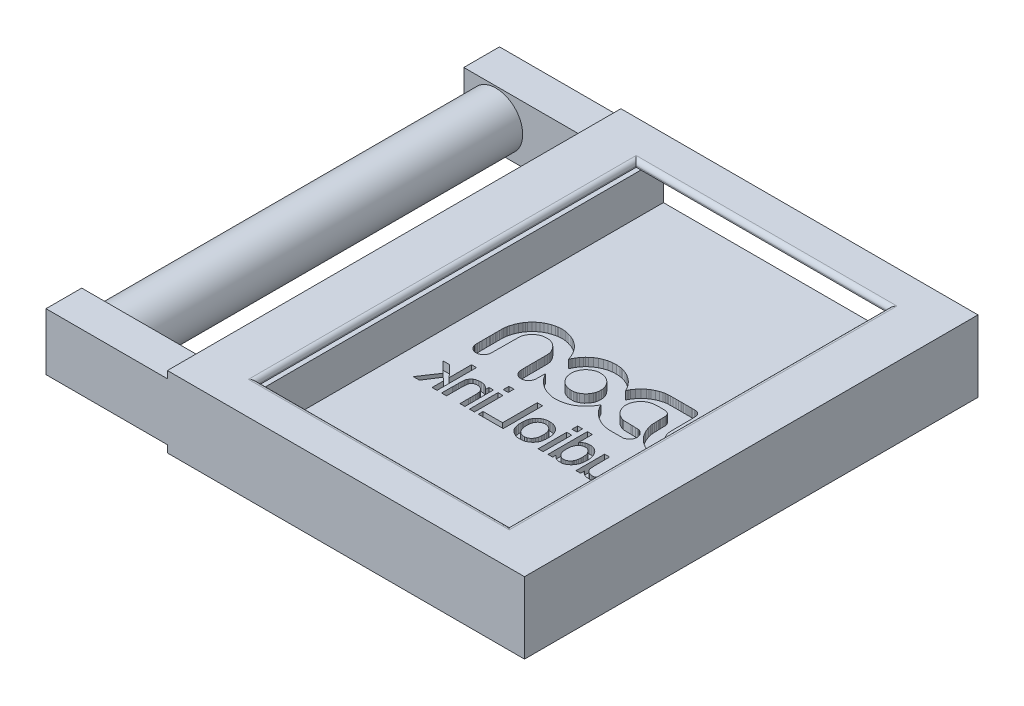
SolidWorks part; units mm, degrees
material "6061 Alloy"
ref_plane "Front" through (0, 0, 0) normal (0, 0, 1) x (1, 0, 0)
ref_plane "Top" through (0, 0, 0) normal (0, 1, 0) x (1, 0, 0)
ref_plane "Right" through (0, 0, 0) normal (1, 0, 0) x (0, 0, -1)
sketch "Sketch1" plane through (0, 0, 0) normal (0, 1, 0) x (1, 0, 0)
  line L1 (-100, -127) -> (100, -127)
  line L2 (-100, -127) -> (-100, 127)
  line L3 (-100, 127) -> (100, 127)
  line L4 (100, -127) -> (100, 127)
  line L5 (-100, -127) -> (100, 127) construction
  line L6 (-100, 127) -> (100, -127) construction
  point P0 (0, 0)
  dimension "D1" = 254
  dimension "D2" = 200
extrude "Boss-Extrude1" add sketch "Sketch1" along normal mid plane 40
sketch "Sketch2" plane through (0, 0, 0) normal (0, 1, 0) x (1, 0, 0)
  line L1 (-100, 127) -> (-168, 127)
  line L2 (-100, 127) -> (-100, 107)
  line L3 (-100, 107) -> (-168, 107)
  line L4 (-168, 127) -> (-168, 107)
  dimension "D1" = 68
  dimension "D2" = 20
extrude "Boss-Extrude2" add sketch "Sketch2" along normal mid plane 32
sketch "Sketch3" plane through (0, 0, 0) normal (0, 0, 1) x (1, 0, 0)
  circle A0 centre (-150, 0) radius 15
  dimension "D1" = 30
  dimension "D2" = 150
extrude "Boss-Extrude3" add sketch "Sketch3" against normal up to surface (107 mm away) up to face at (-134, 0, -107)
mirror "Mirror1" about plane through (0, 0, 0) normal (0, 0, 1) of "Boss-Extrude2", "Boss-Extrude3"
sketch "Sketch4" plane through (0, 20, 0) normal (0, 1, 0) x (1, 0, 0)
  line L1 (-70.485, -106.045) -> (70.485, -106.045)
  line L2 (-70.485, -106.045) -> (-70.485, 106.045)
  line L3 (-70.485, 106.045) -> (70.485, 106.045)
  line L4 (70.485, -106.045) -> (70.485, 106.045)
  line L5 (-70.485, -106.045) -> (70.485, 106.045) construction
  line L6 (-70.485, 106.045) -> (70.485, -106.045) construction
  point P0 (0, 0)
  dimension "D1" = 212.09
  dimension "D2" = 140.97
extrude "Cut-Extrude1" cut sketch "Sketch4" against normal blind 6.35
sketch "Sketch5" plane through (0, 0, 127) normal (0, 0, 1) x (1, 0, 0)
  line L0 (70.485, 13.65) -> (70.485, 20) construction
  line L1 (-87.249, 16.825) -> (87.249, 16.825)
  line L2 (-87.249, 16.825) -> (-87.249, 8.443)
  line L3 (-87.249, 8.443) -> (87.249, 8.443)
  line L4 (87.249, 16.825) -> (87.249, 8.443)
  line L5 (-87.249, 16.825) -> (87.249, 8.443) construction
  line L6 (-87.249, 8.443) -> (87.249, 16.825) construction
  line L7 (-70.485, 13.65) -> (-70.485, 20) construction
  line L8 (70.485, 13.65) -> (70.485, 20) construction
  line L9 (-70.485, 13.65) -> (-70.485, 20) construction
  line L10 (-100, 20) -> (100, 20) construction
  point P0 (0, 12.634)
  dimension "D1" = 8.382
  dimension "D2" = 3.175
  dimension "D3" = 16.764
  dimension "D4" = 16.764
extrude "Cut-Extrude2" cut sketch "Sketch5" along normal offset from surface (249.809 mm away) 16.764 from surface up to face at (0, 16.825, 106.045) offset beyond the face yes starting at face at (-67, 0, -127)
fillet "Fillet1" radius 2.54 4 edges at (0, 20, 106.045) (70.485, 20, 0) (-70.485, 20, 0) (0, 20, -106.045)
sketch "Sketch6" plane through (0, 0, -127) normal (0, 0, -1) x (-1, 0, 0)
  line L0 (87.249, 8.443) -> (-87.249, 8.443) construction
  line L1 (-76.2, -13.65) -> (76.2, -13.65)
  line L2 (-76.2, -13.65) -> (-76.2, 8.443)
  line L3 (-76.2, 8.443) -> (76.2, 8.443)
  line L4 (76.2, -13.65) -> (76.2, 8.443)
  line L5 (-76.2, -13.65) -> (76.2, 8.443) construction
  line L6 (-76.2, 8.443) -> (76.2, -13.65) construction
  line L7 (-100, -20) -> (100, -20) construction
  point P0 (0, -2.6035)
  dimension "D1" = 152.4
  dimension "D2" = 6.35
extrude "Cut-Extrude3" cut sketch "Sketch6" against normal up to surface (249.809 mm away) up to face at (0, 12.634, 122.809)
sketch "Sketch9" plane through (0, -20, 0) normal (0, -1, 0) x (1, 0, 0)
  line L0 (47.93, -1.8124) -> (48.8593, -2.019)
  line L1 (48.8593, -2.019) -> (50.5205, -2.4998)
  line L2 (50.5205, -2.4998) -> (52.0185, -3.112)
  line L3 (52.0185, -3.112) -> (53.4733, -3.9044)
  line L4 (53.4733, -3.9044) -> (54.222, -4.3835)
  line L5 (54.222, -4.3835) -> (54.8334, -4.8153)
  line L6 (54.8334, -4.8153) -> (56.0096, -5.784)
  line L7 (56.0096, -5.784) -> (57.1117, -6.8762)
  line L8 (57.1117, -6.8762) -> (58.1253, -8.0714)
  line L9 (58.1253, -8.0714) -> (59.0359, -9.3494)
  line L10 (59.0359, -9.3494) -> (59.829, -10.6898)
  line L11 (59.829, -10.6898) -> (60.49, -12.0723)
  line L12 (60.49, -12.0723) -> (61.0045, -13.4765)
  line L13 (61.0045, -13.4765) -> (61.2023, -14.1804)
  line L14 (61.2023, -14.1804) -> (61.4, -15.0085)
  line L15 (61.4, -15.0085) -> (61.6145, -16.1928)
  line L16 (61.6145, -16.1928) -> (61.7109, -17.0783)
  line L17 (61.7109, -17.0783) -> (61.7768, -18.1482)
  line L18 (61.7768, -18.1482) -> (61.8178, -19.4948)
  line L19 (61.8178, -19.4948) -> (61.8396, -21.2101)
  line L20 (61.8396, -21.2101) -> (61.8467, -22.7941)
  line L21 (61.8467, -22.7941) -> (61.8484, -24.0134)
  line L22 (61.8484, -24.0134) -> (61.8486, -24.6763)
  line L23 (61.8486, -24.6763) -> (61.8486, -25.2604)
  line L24 (61.8486, -25.2604) -> (61.8482, -26.327)
  line L25 (61.8482, -26.327) -> (61.846, -27.691)
  line L26 (61.846, -27.691) -> (61.8385, -29.1187)
  line L27 (61.8385, -29.1187) -> (61.8233, -30.1692)
  line L28 (61.8233, -30.1692) -> (61.798, -30.9181)
  line L29 (61.798, -30.9181) -> (61.7599, -31.4412)
  line L30 (61.7599, -31.4412) -> (61.6732, -31.9679)
  line L31 (61.6732, -31.9679) -> (61.5921, -32.2575)
  line L32 (61.5921, -32.2575) -> (61.4441, -32.651)
  line L33 (61.4441, -32.651) -> (61.0089, -33.4052)
  line L34 (61.0089, -33.4052) -> (60.4202, -34.0791)
  line L35 (60.4202, -34.0791) -> (59.7166, -34.6283)
  line L36 (59.7166, -34.6283) -> (59.3337, -34.8425)
  line L37 (59.3337, -34.8425) -> (58.9346, -35.0064)
  line L38 (58.9346, -35.0064) -> (58.0614, -35.1964)
  line L39 (58.0614, -35.1964) -> (57.1488, -35.2022)
  line L40 (57.1488, -35.2022) -> (56.2694, -35.0232)
  line L41 (56.2694, -35.0232) -> (55.8648, -34.8643)
  line L42 (55.8648, -34.8643) -> (55.3692, -34.5995)
  line L43 (55.3692, -34.5995) -> (54.5302, -33.9483)
  line L44 (54.5302, -33.9483) -> (53.8984, -33.1408)
  line L45 (53.8984, -33.1408) -> (53.4792, -32.1837)
  line L46 (53.4792, -32.1837) -> (53.351, -31.6514)
  line L47 (53.351, -31.6514) -> (53.3349, -31.5347)
  line L48 (53.3349, -31.5347) -> (53.3054, -31.1451)
  line L49 (53.3054, -31.1451) -> (53.2796, -30.5535)
  line L50 (53.2796, -30.5535) -> (53.2577, -29.7676)
  line L51 (53.2577, -29.7676) -> (53.2397, -28.795)
  line L52 (53.2397, -28.795) -> (53.2258, -27.6434)
  line L53 (53.2258, -27.6434) -> (53.2161, -26.3204)
  line L54 (53.2161, -26.3204) -> (53.2108, -24.8337)
  line L55 (53.2108, -24.8337) -> (53.2099, -24.0314)
  line L56 (53.2099, -24.0314) -> (53.2069, -22.5476)
  line L57 (53.2069, -22.5476) -> (53.1942, -20.5567)
  line L58 (53.1942, -20.5567) -> (53.1807, -19.4123)
  line L59 (53.1807, -19.4123) -> (53.1636, -18.4351)
  line L60 (53.1636, -18.4351) -> (53.1432, -17.6434)
  line L61 (53.1432, -17.6434) -> (53.1198, -17.055)
  line L62 (53.1198, -17.055) -> (53.0937, -16.6882)
  line L63 (53.0937, -16.6882) -> (53.0797, -16.5934)
  line L64 (53.0797, -16.5934) -> (52.8926, -15.8966)
  line L65 (52.8926, -15.8966) -> (52.3521, -14.5891)
  line L66 (52.3521, -14.5891) -> (51.6095, -13.4123)
  line L67 (51.6095, -13.4123) -> (50.6885, -12.385)
  line L68 (50.6885, -12.385) -> (49.6127, -11.5261)
  line L69 (49.6127, -11.5261) -> (48.4057, -10.8544)
  line L70 (48.4057, -10.8544) -> (47.0912, -10.3889)
  line L71 (47.0912, -10.3889) -> (45.6927, -10.1483)
  line L72 (45.6927, -10.1483) -> (44.9694, -10.1183)
  line L73 (44.9694, -10.1183) -> (43.9951, -10.1684)
  line L74 (43.9951, -10.1684) -> (42.185, -10.5837)
  line L75 (42.185, -10.5837) -> (41.2769, -10.9654)
  line L76 (41.2769, -10.9654) -> (40.8053, -11.229)
  line L77 (40.8053, -11.229) -> (39.795, -11.9878)
  line L78 (39.795, -11.9878) -> (38.8185, -12.936)
  line L79 (38.8185, -12.936) -> (38.0234, -13.93)
  line L80 (38.0234, -13.93) -> (37.7401, -14.3995)
  line L81 (37.7401, -14.3995) -> (37.5607, -14.7386)
  line L82 (37.5607, -14.7386) -> (37.2712, -15.3057)
  line L83 (37.2712, -15.3057) -> (37.0622, -15.844)
  line L84 (37.0622, -15.844) -> (36.9192, -16.4977)
  line L85 (36.9192, -16.4977) -> (36.8279, -17.4103)
  line L86 (36.8279, -17.4103) -> (36.7846, -18.3514)
  line L87 (36.7846, -18.3514) -> (36.7643, -19.1346)
  line L88 (36.7643, -19.1346) -> (36.7489, -20.0635)
  line L89 (36.7489, -20.0635) -> (36.7365, -21.1561)
  line L90 (36.7365, -21.1561) -> (36.7253, -22.4303)
  line L91 (36.7253, -22.4303) -> (36.7135, -23.9041)
  line L92 (36.7135, -23.9041) -> (36.7068, -24.7214)
  line L93 (36.7068, -24.7214) -> (36.7002, -25.5284)
  line L94 (36.7002, -25.5284) -> (36.6881, -26.9863)
  line L95 (36.6881, -26.9863) -> (36.6766, -28.2491)
  line L96 (36.6766, -28.2491) -> (36.664, -29.3326)
  line L97 (36.664, -29.3326) -> (36.6488, -30.2526)
  line L98 (36.6488, -30.2526) -> (36.6297, -31.0248)
  line L99 (36.6297, -31.0248) -> (36.5902, -31.9403)
  line L100 (36.5902, -31.9403) -> (36.5095, -32.7906)
  line L101 (36.5095, -32.7906) -> (36.3858, -33.3329)
  line L102 (36.3858, -33.3329) -> (36.0936, -33.8445)
  line L103 (36.0936, -33.8445) -> (35.8102, -34.1679)
  line L104 (35.8102, -34.1679) -> (35.3632, -34.5848)
  line L105 (35.3632, -34.5848) -> (34.8735, -34.9207)
  line L106 (34.8735, -34.9207) -> (34.6857, -35.0125)
  line L107 (34.6857, -35.0125) -> (34.2701, -35.1085)
  line L108 (34.2701, -35.1085) -> (33.7539, -35.1494)
  line L109 (33.7539, -35.1494) -> (32.9267, -35.1756)
  line L110 (32.9267, -35.1756) -> (32.0403, -35.1876)
  line L111 (32.0403, -35.1876) -> (31.2987, -35.1927)
  line L112 (31.2987, -35.1927) -> (30.4215, -35.196)
  line L113 (30.4215, -35.196) -> (29.3959, -35.1979)
  line L114 (29.3959, -35.1979) -> (28.2091, -35.1987)
  line L115 (28.2091, -35.1987) -> (26.8482, -35.1989)
  line L116 (26.8482, -35.1989) -> (26.0985, -35.1989)
  line L117 (26.0985, -35.1989) -> (25.4237, -35.1989)
  line L118 (25.4237, -35.1989) -> (24.1823, -35.1982)
  line L119 (24.1823, -35.1982) -> (22.573, -35.1954)
  line L120 (22.573, -35.1954) -> (20.8496, -35.1874)
  line L121 (20.8496, -35.1874) -> (19.5398, -35.1726)
  line L122 (19.5398, -35.1726) -> (18.5682, -35.1492)
  line L123 (18.5682, -35.1492) -> (17.8592, -35.1155)
  line L124 (17.8592, -35.1155) -> (17.1232, -35.0417)
  line L125 (17.1232, -35.0417) -> (16.7409, -34.9742)
  line L126 (16.7409, -34.9742) -> (15.8881, -34.7797)
  line L127 (15.8881, -34.7797) -> (14.2327, -34.2776)
  line L128 (14.2327, -34.2776) -> (12.6521, -33.628)
  line L129 (12.6521, -33.628) -> (11.1562, -32.8348)
  line L130 (11.1562, -32.8348) -> (10.443, -32.3856)
  line L131 (10.443, -32.3856) -> (9.6232, -31.7926)
  line L132 (9.6232, -31.7926) -> (8.0064, -30.3585)
  line L133 (8.0064, -30.3585) -> (6.5288, -28.7146)
  line L134 (6.5288, -28.7146) -> (5.3208, -27.006)
  line L135 (5.3208, -27.006) -> (4.8587, -26.1729)
  line L136 (4.8587, -26.1729) -> (4.4117, -25.2748)
  line L137 (4.4117, -25.2748) -> (3.998, -26.0686)
  line L138 (3.998, -26.0686) -> (3.5333, -26.9017)
  line L139 (3.5333, -26.9017) -> (2.4731, -28.475)
  line L140 (2.4731, -28.475) -> (1.2523, -29.914)
  line L141 (1.2523, -29.914) -> (-0.1132, -31.2064)
  line L142 (-0.1132, -31.2064) -> (-1.607, -32.34)
  line L143 (-1.607, -32.34) -> (-3.2132, -33.3026)
  line L144 (-3.2132, -33.3026) -> (-4.9154, -34.0818)
  line L145 (-4.9154, -34.0818) -> (-6.6976, -34.6655)
  line L146 (-6.6976, -34.6655) -> (-7.6137, -34.8801)
  line L147 (-7.6137, -34.8801) -> (-8.6686, -35.0616)
  line L148 (-8.6686, -35.0616) -> (-10.7713, -35.2252)
  line L149 (-10.7713, -35.2252) -> (-12.8491, -35.1279)
  line L150 (-12.8491, -35.1279) -> (-14.8833, -34.7755)
  line L151 (-14.8833, -34.7755) -> (-16.8553, -34.1736)
  line L152 (-16.8553, -34.1736) -> (-18.7463, -33.3279)
  line L153 (-18.7463, -33.3279) -> (-20.5378, -32.2442)
  line L154 (-20.5378, -32.2442) -> (-22.2109, -30.9281)
  line L155 (-22.2109, -30.9281) -> (-22.9973, -30.1847)
  line L156 (-22.9973, -30.1847) -> (-23.5248, -29.6247)
  line L157 (-23.5248, -29.6247) -> (-24.5397, -28.3737)
  line L158 (-24.5397, -28.3737) -> (-25.4499, -27.0237)
  line L159 (-25.4499, -27.0237) -> (-26.1944, -25.6654)
  line L160 (-26.1944, -25.6654) -> (-26.4854, -25.0115)
  line L161 (-26.4854, -25.0115) -> (-26.7632, -24.328)
  line L162 (-26.7632, -24.328) -> (-27.0924, -25.382)
  line L163 (-27.0924, -25.382) -> (-27.4778, -26.465)
  line L164 (-27.4778, -26.465) -> (-28.506, -28.5948)
  line L165 (-28.506, -28.5948) -> (-29.8176, -30.5858)
  line L166 (-29.8176, -30.5858) -> (-31.3414, -32.3296)
  line L167 (-31.3414, -32.3296) -> (-32.1605, -33.075)
  line L168 (-32.1605, -33.075) -> (-33.1539, -33.8619)
  line L169 (-33.1539, -33.8619) -> (-35.1274, -35.1509)
  line L170 (-35.1274, -35.1509) -> (-37.1834, -36.1065)
  line L171 (-37.1834, -36.1065) -> (-39.442, -36.7846)
  line L172 (-39.442, -36.7846) -> (-40.6848, -37.0371)
  line L173 (-40.6848, -37.0371) -> (-41.3523, -37.1437)
  line L174 (-41.3523, -37.1437) -> (-42.5862, -37.2657)
  line L175 (-42.5862, -37.2657) -> (-43.7685, -37.2661)
  line L176 (-43.7685, -37.2661) -> (-44.9993, -37.1451)
  line L177 (-44.9993, -37.1451) -> (-45.6641, -37.0391)
  line L178 (-45.6641, -37.0391) -> (-46.5297, -36.868)
  line L179 (-46.5297, -36.868) -> (-48.1852, -36.4278)
  line L180 (-48.1852, -36.4278) -> (-49.7428, -35.8549)
  line L181 (-49.7428, -35.8549) -> (-51.2063, -35.1471)
  line L182 (-51.2063, -35.1471) -> (-52.5794, -34.302)
  line L183 (-52.5794, -34.302) -> (-53.8658, -33.3174)
  line L184 (-53.8658, -33.3174) -> (-55.0694, -32.1909)
  line L185 (-55.0694, -32.1909) -> (-56.1937, -30.9202)
  line L186 (-56.1937, -30.9202) -> (-56.7274, -30.2301)
  line L187 (-56.7274, -30.2301) -> (-57.2616, -29.4642)
  line L188 (-57.2616, -29.4642) -> (-58.1905, -27.8525)
  line L189 (-58.1905, -27.8525) -> (-58.9425, -26.1127)
  line L190 (-58.9425, -26.1127) -> (-59.5287, -24.2193)
  line L191 (-59.5287, -24.2193) -> (-59.7631, -23.2069)
  line L192 (-59.7631, -23.2069) -> (-59.8639, -22.7055)
  line L193 (-59.8639, -22.7055) -> (-59.9693, -21.9562)
  line L194 (-59.9693, -21.9562) -> (-60.0143, -21.2913)
  line L195 (-60.0143, -21.2913) -> (-60.0433, -20.3602)
  line L196 (-60.0433, -20.3602) -> (-60.0598, -19.0481)
  line L197 (-60.0598, -19.0481) -> (-60.0662, -17.7451)
  line L198 (-60.0662, -17.7451) -> (-60.0684, -16.6976)
  line L199 (-60.0684, -16.6976) -> (-60.0695, -15.4904)
  line L200 (-60.0695, -15.4904) -> (-60.0699, -14.109)
  line L201 (-60.0699, -14.109) -> (-60.07, -13.3486)
  line L202 (-60.07, -13.3486) -> (-60.0679, -11.6508)
  line L203 (-60.0679, -11.6508) -> (-60.057, -9.3283)
  line L204 (-60.057, -9.3283) -> (-60.0452, -7.9785)
  line L205 (-60.0452, -7.9785) -> (-60.0302, -6.8266)
  line L206 (-60.0302, -6.8266) -> (-60.0125, -5.9063)
  line L207 (-60.0125, -5.9063) -> (-59.9926, -5.2512)
  line L208 (-59.9926, -5.2512) -> (-59.9708, -4.8951)
  line L209 (-59.9708, -4.8951) -> (-59.9593, -4.8396)
  line L210 (-59.9593, -4.8396) -> (-59.9043, -4.756)
  line L211 (-59.9043, -4.756) -> (-59.7656, -4.4437)
  line L212 (-59.7656, -4.4437) -> (-59.699, -4.2534)
  line L213 (-59.699, -4.2534) -> (-59.6021, -4.0237)
  line L214 (-59.6021, -4.0237) -> (-59.2623, -3.4944)
  line L215 (-59.2623, -3.4944) -> (-58.5336, -2.6951)
  line L216 (-58.5336, -2.6951) -> (-58.0151, -2.2908)
  line L217 (-58.0151, -2.2908) -> (-57.7273, -2.1311)
  line L218 (-57.7273, -2.1311) -> (-57.055, -1.8689)
  line L219 (-57.055, -1.8689) -> (-56.3263, -1.7002)
  line L220 (-56.3263, -1.7002) -> (-55.6278, -1.6448)
  line L221 (-55.6278, -1.6448) -> (-55.3171, -1.666)
  line L222 (-55.3171, -1.666) -> (-54.7785, -1.7767)
  line L223 (-54.7785, -1.7767) -> (-53.7585, -2.2139)
  line L224 (-53.7585, -2.2139) -> (-52.8596, -2.9046)
  line L225 (-52.8596, -2.9046) -> (-52.136, -3.807)
  line L226 (-52.136, -3.807) -> (-51.8568, -4.3246)
  line L227 (-51.8568, -4.3246) -> (-51.4985, -5.0999)
  line L228 (-51.4985, -5.0999) -> (-51.4312, -13.6724)
  line L229 (-51.4312, -13.6724) -> (-51.4252, -14.4369)
  line L230 (-51.4252, -14.4369) -> (-51.4139, -15.8277)
  line L231 (-51.4139, -15.8277) -> (-51.4034, -17.0448)
  line L232 (-51.4034, -17.0448) -> (-51.393, -18.101)
  line L233 (-51.393, -18.101) -> (-51.3824, -19.0094)
  line L234 (-51.3824, -19.0094) -> (-51.371, -19.7826)
  line L235 (-51.371, -19.7826) -> (-51.3516, -20.7173)
  line L236 (-51.3516, -20.7173) -> (-51.3186, -21.6106)
  line L237 (-51.3186, -21.6106) -> (-51.2741, -22.1949)
  line L238 (-51.2741, -22.1949) -> (-51.1775, -22.7169)
  line L239 (-51.1775, -22.7169) -> (-51.0877, -22.9784)
  line L240 (-51.0877, -22.9784) -> (-50.776, -23.7156)
  line L241 (-50.776, -23.7156) -> (-49.9983, -25.0764)
  line L242 (-49.9983, -25.0764) -> (-49.0459, -26.2477)
  line L243 (-49.0459, -26.2477) -> (-47.9559, -27.1837)
  line L244 (-47.9559, -27.1837) -> (-47.371, -27.5492)
  line L245 (-47.371, -27.5492) -> (-46.8306, -27.8335)
  line L246 (-46.8306, -27.8335) -> (-45.853, -28.2463)
  line L247 (-45.853, -28.2463) -> (-44.8852, -28.4825)
  line L248 (-44.8852, -28.4825) -> (-43.7739, -28.5794)
  line L249 (-43.7739, -28.5794) -> (-43.1165, -28.5874)
  line L250 (-43.1165, -28.5874) -> (-42.6016, -28.5831)
  line L251 (-42.6016, -28.5831) -> (-41.8473, -28.5534)
  line L252 (-41.8473, -28.5534) -> (-41.2968, -28.4714)
  line L253 (-41.2968, -28.4714) -> (-40.7543, -28.3077)
  line L254 (-40.7543, -28.3077) -> (-40.4247, -28.186)
  line L255 (-40.4247, -28.186) -> (-39.9657, -27.9967)
  line L256 (-39.9657, -27.9967) -> (-39.0406, -27.5409)
  line L257 (-39.0406, -27.5409) -> (-38.6885, -27.3306)
  line L258 (-38.6885, -27.3306) -> (-38.2703, -27.0276)
  line L259 (-38.2703, -27.0276) -> (-37.4493, -26.2898)
  line L260 (-37.4493, -26.2898) -> (-36.6972, -25.4315)
  line L261 (-36.6972, -25.4315) -> (-36.0723, -24.5191)
  line L262 (-36.0723, -24.5191) -> (-35.8257, -24.0634)
  line L263 (-35.8257, -24.0634) -> (-35.5228, -23.4356)
  line L264 (-35.5228, -23.4356) -> (-35.2091, -22.5816)
  line L265 (-35.2091, -22.5816) -> (-35.0772, -21.8826)
  line L266 (-35.0772, -21.8826) -> (-34.9942, -20.9297)
  line L267 (-34.9942, -20.9297) -> (-34.9571, -19.9706)
  line L268 (-34.9571, -19.9706) -> (-34.9417, -19.1848)
  line L269 (-34.9417, -19.1848) -> (-34.9322, -18.2629)
  line L270 (-34.9322, -18.2629) -> (-34.9272, -17.1889)
  line L271 (-34.9272, -17.1889) -> (-34.9253, -15.9467)
  line L272 (-34.9253, -15.9467) -> (-34.925, -14.52)
  line L273 (-34.925, -14.52) -> (-34.925, -13.7326)
  line L274 (-34.925, -13.7326) -> (-34.9244, -12.8119)
  line L275 (-34.9244, -12.8119) -> (-34.9199, -11.1176)
  line L276 (-34.9199, -11.1176) -> (-34.911, -9.6236)
  line L277 (-34.911, -9.6236) -> (-34.8978, -8.335)
  line L278 (-34.8978, -8.335) -> (-34.8803, -7.2571)
  line L279 (-34.8803, -7.2571) -> (-34.8587, -6.3951)
  line L280 (-34.8587, -6.3951) -> (-34.833, -5.7541)
  line L281 (-34.833, -5.7541) -> (-34.8033, -5.3394)
  line L282 (-34.8033, -5.3394) -> (-34.787, -5.2185)
  line L283 (-34.787, -5.2185) -> (-34.6999, -4.8323)
  line L284 (-34.6999, -4.8323) -> (-34.4399, -4.1124)
  line L285 (-34.4399, -4.1124) -> (-34.0739, -3.4695)
  line L286 (-34.0739, -3.4695) -> (-33.6116, -2.9118)
  line L287 (-33.6116, -2.9118) -> (-33.063, -2.4477)
  line L288 (-33.063, -2.4477) -> (-32.4378, -2.0856)
  line L289 (-32.4378, -2.0856) -> (-31.746, -1.8338)
  line L290 (-31.746, -1.8338) -> (-30.9973, -1.7005)
  line L291 (-30.9973, -1.7005) -> (-30.6047, -1.681)
  line L292 (-30.6047, -1.681) -> (-29.981, -1.7185)
  line L293 (-29.981, -1.7185) -> (-28.8386, -2.046)
  line L294 (-28.8386, -2.046) -> (-27.851, -2.7004)
  line L295 (-27.851, -2.7004) -> (-27.0358, -3.6702)
  line L296 (-27.0358, -3.6702) -> (-26.6984, -4.2697)
  line L297 (-26.6984, -4.2697) -> (-26.585, -4.5073)
  line L298 (-26.585, -4.5073) -> (-26.4362, -4.9681)
  line L299 (-26.4362, -4.9681) -> (-26.3751, -5.4722)
  line L300 (-26.3751, -5.4722) -> (-26.3502, -5.9652)
  line L301 (-26.3502, -5.9652) -> (-26.3328, -6.6345)
  line L302 (-26.3328, -6.6345) -> (-26.3184, -7.5234)
  line L303 (-26.3184, -7.5234) -> (-26.3109, -8.0637)
  line L304 (-26.3109, -8.0637) -> (-26.2689, -11.1546)
  line L305 (-26.2689, -11.1546) -> (-25.7104, -10.1744)
  line L306 (-25.7104, -10.1744) -> (-25.2365, -9.3917)
  line L307 (-25.2365, -9.3917) -> (-24.177, -7.917)
  line L308 (-24.177, -7.917) -> (-22.9796, -6.5718)
  line L309 (-22.9796, -6.5718) -> (-21.6581, -5.3662)
  line L310 (-21.6581, -5.3662) -> (-20.2262, -4.3101)
  line L311 (-20.2262, -4.3101) -> (-18.6974, -3.4138)
  line L312 (-18.6974, -3.4138) -> (-17.0854, -2.6873)
  line L313 (-17.0854, -2.6873) -> (-15.404, -2.1406)
  line L314 (-15.404, -2.1406) -> (-14.5415, -1.9379)
  line L315 (-14.5415, -1.9379) -> (-14.0986, -1.847)
  line L316 (-14.0986, -1.847) -> (-13.2307, -1.6695)
  line L317 (-13.2307, -1.6695) -> (-12.9126, -1.6047)
  line L318 (-12.9126, -1.6047) -> (-12.466, -1.5337)
  line L319 (-12.466, -1.5337) -> (-11.4389, -1.475)
  line L320 (-11.4389, -1.475) -> (-9.655, -1.5789)
  line L321 (-9.655, -1.5789) -> (-7.0806, -2.0304)
  line L322 (-7.0806, -2.0304) -> (-5.2179, -2.5662)
  line L323 (-5.2179, -2.5662) -> (-4.1006, -3.001)
  line L324 (-4.1006, -3.001) -> (-3.5977, -3.2385)
  line L325 (-3.5977, -3.2385) -> (-2.4454, -3.8854)
  line L326 (-2.4454, -3.8854) -> (-0.2515, -5.484)
  line L327 (-0.2515, -5.484) -> (1.7045, -7.4005)
  line L328 (1.7045, -7.4005) -> (3.3142, -9.5288)
  line L329 (3.3142, -9.5288) -> (3.9552, -10.6392)
  line L330 (3.9552, -10.6392) -> (4.3904, -11.4794)
  line L331 (4.3904, -11.4794) -> (4.9413, -10.4279)
  line L332 (4.9413, -10.4279) -> (5.3263, -9.7401)
  line L333 (5.3263, -9.7401) -> (6.2161, -8.4126)
  line L334 (6.2161, -8.4126) -> (7.2502, -7.1614)
  line L335 (7.2502, -7.1614) -> (8.4106, -6.0016)
  line L336 (8.4106, -6.0016) -> (9.6792, -4.9484)
  line L337 (9.6792, -4.9484) -> (11.0377, -4.0168)
  line L338 (11.0377, -4.0168) -> (12.468, -3.2219)
  line L339 (12.468, -3.2219) -> (13.9519, -2.5787)
  line L340 (13.9519, -2.5787) -> (14.7084, -2.3187)
  line L341 (14.7084, -2.3187) -> (15.5331, -2.0749)
  line L342 (15.5331, -2.0749) -> (17.1024, -1.7339)
  line L343 (17.1024, -1.7339) -> (18.4035, -1.5869)
  line L344 (18.4035, -1.5869) -> (19.4225, -1.5316)
  line L345 (19.4225, -1.5316) -> (20.6203, -1.5047)
  line L346 (20.6203, -1.5047) -> (22.0461, -1.5013)
  line L347 (22.0461, -1.5013) -> (22.86, -1.5068)
  line L348 (22.86, -1.5068) -> (26.9875, -1.5439)
  line L349 (26.9875, -1.5439) -> (27.7793, -1.9096)
  line L350 (27.7793, -1.9096) -> (28.2315, -2.1493)
  line L351 (28.2315, -2.1493) -> (29.0123, -2.7454)
  line L352 (29.0123, -2.7454) -> (29.621, -3.4699)
  line L353 (29.621, -3.4699) -> (30.0487, -4.2897)
  line L354 (30.0487, -4.2897) -> (30.2865, -5.172)
  line L355 (30.2865, -5.172) -> (30.3255, -6.0836)
  line L356 (30.3255, -6.0836) -> (30.1568, -6.9916)
  line L357 (30.1568, -6.9916) -> (29.7716, -7.8632)
  line L358 (29.7716, -7.8632) -> (29.495, -8.2749)
  line L359 (29.495, -8.2749) -> (29.0358, -8.7861)
  line L360 (29.0358, -8.7861) -> (27.8992, -9.6272)
  line L361 (27.8992, -9.6272) -> (27.3275, -9.8789)
  line L362 (27.3275, -9.8789) -> (27.2543, -9.8968)
  line L363 (27.2543, -9.8968) -> (27.0073, -9.9317)
  line L364 (27.0073, -9.9317) -> (26.3933, -9.981)
  line L365 (26.3933, -9.981) -> (25.1434, -10.0404)
  line L366 (25.1434, -10.0404) -> (23.4327, -10.0907)
  line L367 (23.4327, -10.0907) -> (22.4155, -10.1121)
  line L368 (22.4155, -10.1121) -> (17.9705, -10.1949)
  line L369 (17.9705, -10.1949) -> (17.0207, -10.5531)
  line L370 (17.0207, -10.5531) -> (16.3324, -10.846)
  line L371 (16.3324, -10.846) -> (15.0675, -11.5821)
  line L372 (15.0675, -11.5821) -> (13.9649, -12.4963)
  line L373 (13.9649, -12.4963) -> (13.0414, -13.5613)
  line L374 (13.0414, -13.5613) -> (12.3136, -14.7502)
  line L375 (12.3136, -14.7502) -> (11.7978, -16.0359)
  line L376 (11.7978, -16.0359) -> (11.5108, -17.3913)
  line L377 (11.5108, -17.3913) -> (11.4692, -18.7893)
  line L378 (11.4692, -18.7893) -> (11.5455, -19.4959)
  line L379 (11.5455, -19.4959) -> (11.6767, -20.1945)
  line L380 (11.6767, -20.1945) -> (12.0623, -21.4564)
  line L381 (12.0623, -21.4564) -> (12.6362, -22.5846)
  line L382 (12.6362, -22.5846) -> (13.4271, -23.6357)
  line L383 (13.4271, -23.6357) -> (13.9129, -24.1499)
  line L384 (13.9129, -24.1499) -> (14.2939, -24.5126)
  line L385 (14.2939, -24.5126) -> (15.0462, -25.1282)
  line L386 (15.0462, -25.1282) -> (16.2354, -25.8314)
  line L387 (16.2354, -25.8314) -> (17.1352, -26.1956)
  line L388 (17.1352, -26.1956) -> (17.6372, -26.3521)
  line L389 (17.6372, -26.3521) -> (18.7495, -26.5798)
  line L390 (18.7495, -26.5798) -> (20.1313, -26.7051)
  line L391 (20.1313, -26.7051) -> (21.4348, -26.7401)
  line L392 (21.4348, -26.7401) -> (22.4663, -26.7384)
  line L393 (22.4663, -26.7384) -> (23.0378, -26.7308)
  line L394 (23.0378, -26.7308) -> (23.5826, -26.7212)
  line L395 (23.5826, -26.7212) -> (24.4877, -26.6984)
  line L396 (24.4877, -26.6984) -> (25.1826, -26.6629)
  line L397 (25.1826, -26.6629) -> (25.7101, -26.6053)
  line L398 (25.7101, -26.6053) -> (26.2808, -26.4567)
  line L399 (26.2808, -26.4567) -> (26.8544, -26.0928)
  line L400 (26.8544, -26.0928) -> (27.1571, -25.8185)
  line L401 (27.1571, -25.8185) -> (27.4357, -25.5494)
  line L402 (27.4357, -25.5494) -> (27.7976, -24.9893)
  line L403 (27.7976, -24.9893) -> (27.9422, -24.292)
  line L404 (27.9422, -24.292) -> (27.9993, -23.5723)
  line L405 (27.9993, -23.5723) -> (28.0381, -22.5723)
  line L406 (28.0381, -22.5723) -> (28.0698, -21.2265)
  line L407 (28.0698, -21.2265) -> (28.0865, -20.4034)
  line L408 (28.0865, -20.4034) -> (28.0982, -19.8547)
  line L409 (28.0982, -19.8547) -> (28.1231, -18.861)
  line L410 (28.1231, -18.861) -> (28.1652, -17.6148)
  line L411 (28.1652, -17.6148) -> (28.2323, -16.3682)
  line L412 (28.2323, -16.3682) -> (28.3151, -15.5383)
  line L413 (28.3151, -15.5383) -> (28.3635, -15.2599)
  line L414 (28.3635, -15.2599) -> (28.7437, -13.783)
  line L415 (28.7437, -13.783) -> (29.837, -11.001)
  line L416 (29.837, -11.001) -> (31.3485, -8.4905)
  line L417 (31.3485, -8.4905) -> (32.7383, -6.8163)
  line L418 (32.7383, -6.8163) -> (33.7796, -5.8114)
  line L419 (33.7796, -5.8114) -> (34.3332, -5.3448)
  line L420 (34.3332, -5.3448) -> (35.1932, -4.6885)
  line L421 (35.1932, -4.6885) -> (36.9311, -3.5871)
  line L422 (36.9311, -3.5871) -> (38.7596, -2.7366)
  line L423 (38.7596, -2.7366) -> (40.7584, -2.0999)
  line L424 (40.7584, -2.0999) -> (41.8465, -1.85)
  line L425 (41.8465, -1.85) -> (42.6782, -1.6958)
  line L426 (42.6782, -1.6958) -> (44.211, -1.5159)
  line L427 (44.211, -1.5159) -> (45.6624, -1.507)
  line L428 (45.6624, -1.507) -> (47.1435, -1.6682)
  line L429 (47.1435, -1.6682) -> (47.93, -1.8124)
  line L430 (22.479, 27.6239) -> (22.8987, 27.475)
  line L431 (22.8987, 27.475) -> (23.6208, 27.1527)
  line L432 (23.6208, 27.1527) -> (24.2551, 26.7544)
  line L433 (24.2551, 26.7544) -> (24.884, 26.2286)
  line L434 (24.884, 26.2286) -> (25.2222, 25.9016)
  line L435 (25.2222, 25.9016) -> (25.5751, 25.5248)
  line L436 (25.5751, 25.5248) -> (26.1896, 24.7175)
  line L437 (26.1896, 24.7175) -> (26.6918, 23.8219)
  line L438 (26.6918, 23.8219) -> (27.0931, 22.8177)
  line L439 (27.0931, 22.8177) -> (27.2595, 22.2686)
  line L440 (27.2595, 22.2686) -> (27.3162, 22.0251)
  line L441 (27.3162, 22.0251) -> (27.407, 21.4175)
  line L442 (27.407, 21.4175) -> (27.4863, 20.2929)
  line L443 (27.4863, 20.2929) -> (27.4858, 18.6436)
  line L444 (27.4858, 18.6436) -> (27.4058, 17.5012)
  line L445 (27.4058, 17.5012) -> (27.3146, 16.8732)
  line L446 (27.3146, 16.8732) -> (27.2577, 16.6171)
  line L447 (27.2577, 16.6171) -> (27.0032, 15.7815)
  line L448 (27.0032, 15.7815) -> (26.3203, 14.2855)
  line L449 (26.3203, 14.2855) -> (25.4256, 13.0509)
  line L450 (25.4256, 13.0509) -> (24.3438, 12.1115)
  line L451 (24.3438, 12.1115) -> (23.7403, 11.7631)
  line L452 (23.7403, 11.7631) -> (23.3338, 11.5756)
  line L453 (23.3338, 11.5756) -> (22.5586, 11.3014)
  line L454 (22.5586, 11.3014) -> (21.7685, 11.1489)
  line L455 (21.7685, 11.1489) -> (20.8854, 11.1028)
  line L456 (20.8854, 11.1028) -> (20.3844, 11.115)
  line L457 (20.3844, 11.115) -> (20.0415, 11.1329)
  line L458 (20.0415, 11.1329) -> (19.5012, 11.1873)
  line L459 (19.5012, 11.1873) -> (18.8608, 11.3595)
  line L460 (18.8608, 11.3595) -> (18.396, 11.5692)
  line L461 (18.396, 11.5692) -> (17.6424, 12.0268)
  line L462 (17.6424, 12.0268) -> (16.9802, 12.5609)
  line L463 (16.9802, 12.5609) -> (16.383, 13.1497)
  line L464 (16.383, 13.1497) -> (16.383, 9.2636)
  line L465 (16.383, 9.2636) -> (16.383, 5.3776)
  line L466 (16.383, 5.3776) -> (14.986, 5.3776)
  line L467 (14.986, 5.3776) -> (13.589, 5.3776)
  line L468 (13.589, 5.3776) -> (13.589, 16.4266)
  line L469 (13.589, 16.4266) -> (13.589, 27.4756)
  line L470 (13.589, 27.4756) -> (14.9225, 27.4756)
  line L471 (14.9225, 27.4756) -> (16.256, 27.4756)
  line L472 (16.256, 27.4756) -> (16.256, 26.592)
  line L473 (16.256, 26.592) -> (16.256, 25.7085)
  line L474 (16.256, 25.7085) -> (16.8459, 26.3391)
  line L475 (16.8459, 26.3391) -> (17.1471, 26.6263)
  line L476 (17.1471, 26.6263) -> (17.8866, 27.1671)
  line L477 (17.8866, 27.1671) -> (18.2698, 27.3803)
  line L478 (18.2698, 27.3803) -> (18.7579, 27.6029)
  line L479 (18.7579, 27.6029) -> (19.4199, 27.7687)
  line L480 (19.4199, 27.7687) -> (20.0305, 27.8114)
  line L481 (20.0305, 27.8114) -> (20.4421, 27.8237)
  line L482 (20.4421, 27.8237) -> (20.8023, 27.8296)
  line L483 (20.8023, 27.8296) -> (21.3963, 27.8185)
  line L484 (21.3963, 27.8185) -> (22.0791, 27.7338)
  line L485 (22.0791, 27.7338) -> (22.479, 27.6239)
  line L486 (0.2993, 27.6553) -> (1.0056, 27.441)
  line L487 (1.0056, 27.441) -> (2.3336, 26.7855)
  line L488 (2.3336, 26.7855) -> (3.4968, 25.8685)
  line L489 (3.4968, 25.8685) -> (4.4331, 24.7391)
  line L490 (4.4331, 24.7391) -> (4.7966, 24.1101)
  line L491 (4.7966, 24.1101) -> (5.0057, 23.6647)
  line L492 (5.0057, 23.6647) -> (5.3258, 22.7767)
  line L493 (5.3258, 22.7767) -> (5.5336, 21.806)
  line L494 (5.5336, 21.806) -> (5.6512, 20.6494)
  line L495 (5.6512, 20.6494) -> (5.683, 19.9691)
  line L496 (5.683, 19.9691) -> (5.6979, 19.1586)
  line L497 (5.6979, 19.1586) -> (5.6354, 17.7727)
  line L498 (5.6354, 17.7727) -> (5.4312, 16.5926)
  line L499 (5.4312, 16.5926) -> (5.0632, 15.4892)
  line L500 (5.0632, 15.4892) -> (4.8107, 14.9259)
  line L501 (4.8107, 14.9259) -> (4.5421, 14.4178)
  line L502 (4.5421, 14.4178) -> (3.9128, 13.5164)
  line L503 (3.9128, 13.5164) -> (3.1506, 12.7581)
  line L504 (3.1506, 12.7581) -> (2.2435, 12.1308)
  line L505 (2.2435, 12.1308) -> (1.7317, 11.8626)
  line L506 (1.7317, 11.8626) -> (1.2778, 11.656)
  line L507 (1.2778, 11.656) -> (0.4519, 11.3533)
  line L508 (0.4519, 11.3533) -> (-0.3621, 11.1771)
  line L509 (-0.3621, 11.1771) -> (-1.2809, 11.102)
  line L510 (-1.2809, 11.102) -> (-1.816, 11.0944)
  line L511 (-1.816, 11.0944) -> (-2.4479, 11.1159)
  line L512 (-2.4479, 11.1159) -> (-3.6445, 11.2798)
  line L513 (-3.6445, 11.2798) -> (-4.7465, 11.6015)
  line L514 (-4.7465, 11.6015) -> (-5.7479, 12.0769)
  line L515 (-5.7479, 12.0769) -> (-6.6427, 12.7016)
  line L516 (-6.6427, 12.7016) -> (-7.4249, 13.4715)
  line L517 (-7.4249, 13.4715) -> (-8.0885, 14.3824)
  line L518 (-8.0885, 14.3824) -> (-8.6273, 15.4301)
  line L519 (-8.6273, 15.4301) -> (-8.8481, 16.0039)
  line L520 (-8.8481, 16.0039) -> (-9.0313, 16.5932)
  line L521 (-9.0313, 16.5932) -> (-9.1787, 17.5052)
  line L522 (-9.1787, 17.5052) -> (-9.2267, 18.3941)
  line L523 (-9.2267, 18.3941) -> (-9.2446, 18.9903)
  line L524 (-9.2446, 18.9903) -> (-9.2554, 19.8309)
  line L525 (-9.2554, 19.8309) -> (-9.1924, 21.2543)
  line L526 (-9.1924, 21.2543) -> (-9.0002, 22.4368)
  line L527 (-9.0002, 22.4368) -> (-8.6586, 23.5017)
  line L528 (-8.6586, 23.5017) -> (-8.4256, 24.0285)
  line L529 (-8.4256, 24.0285) -> (-8.0707, 24.6639)
  line L530 (-8.0707, 24.6639) -> (-7.1311, 25.8054)
  line L531 (-7.1311, 25.8054) -> (-5.9292, 26.7403)
  line L532 (-5.9292, 26.7403) -> (-4.5186, 27.4269)
  line L533 (-4.5186, 27.4269) -> (-3.7516, 27.6642)
  line L534 (-3.7516, 27.6642) -> (-3.3479, 27.7427)
  line L535 (-3.3479, 27.7427) -> (-2.321, 27.8312)
  line L536 (-2.321, 27.8312) -> (-1.1768, 27.8287)
  line L537 (-1.1768, 27.8287) -> (-0.1256, 27.7357)
  line L538 (-0.1256, 27.7357) -> (0.2993, 27.6553)
  line L539 (63.5569, 26.3643) -> (63.4932, 26.1997)
  line L540 (63.4932, 26.1997) -> (63.2571, 25.5875)
  line L541 (63.2571, 25.5875) -> (62.8908, 24.6356)
  line L542 (62.8908, 24.6356) -> (62.4116, 23.3892)
  line L543 (62.4116, 23.3892) -> (61.8368, 21.8934)
  line L544 (61.8368, 21.8934) -> (61.1838, 20.1935)
  line L545 (61.1838, 20.1935) -> (60.0957, 17.3597)
  line L546 (60.0957, 17.3597) -> (59.3232, 15.3471)
  line L547 (59.3232, 15.3471) -> (55.5217, 5.4411)
  line L548 (55.5217, 5.4411) -> (53.8743, 5.4057)
  line L549 (53.8743, 5.4057) -> (53.4453, 5.3985)
  line L550 (53.4453, 5.3985) -> (52.7982, 5.4018)
  line L551 (52.7982, 5.4018) -> (52.3968, 5.4316)
  line L552 (52.3968, 5.4316) -> (52.198, 5.491)
  line L553 (52.198, 5.491) -> (52.1612, 5.5327)
  line L554 (52.1612, 5.5327) -> (52.1124, 5.6527)
  line L555 (52.1124, 5.6527) -> (51.8841, 6.2124)
  line L556 (51.8841, 6.2124) -> (51.5015, 7.1497)
  line L557 (51.5015, 7.1497) -> (50.9886, 8.4057)
  line L558 (50.9886, 8.4057) -> (50.3694, 9.9219)
  line L559 (50.3694, 9.9219) -> (49.6678, 11.6395)
  line L560 (49.6678, 11.6395) -> (48.5134, 14.4652)
  line L561 (48.5134, 14.4652) -> (46.91, 18.3897)
  line L562 (46.91, 18.3897) -> (45.7641, 21.1941)
  line L563 (45.7641, 21.1941) -> (45.0721, 22.8873)
  line L564 (45.0721, 22.8873) -> (44.4657, 24.371)
  line L565 (44.4657, 24.371) -> (43.9688, 25.5865)
  line L566 (43.9688, 25.5865) -> (43.6054, 26.475)
  line L567 (43.6054, 26.475) -> (43.3995, 26.9779)
  line L568 (43.3995, 26.9779) -> (43.3632, 27.0664)
  line L569 (43.3632, 27.0664) -> (43.19, 27.4827)
  line L570 (43.19, 27.4827) -> (44.9249, 27.4474)
  line L571 (44.9249, 27.4474) -> (46.6599, 27.4121)
  line L572 (46.6599, 27.4121) -> (47.9301, 24.0768)
  line L573 (47.9301, 24.0768) -> (49.2004, 20.7415)
  line L574 (49.2004, 20.7415) -> (53.7784, 20.7748)
  line L575 (53.7784, 20.7748) -> (58.3565, 20.8081)
  line L576 (58.3565, 20.8081) -> (59.563, 24.1414)
  line L577 (59.563, 24.1414) -> (60.7695, 27.4747)
  line L578 (60.7695, 27.4747) -> (62.3793, 27.4752)
  line L579 (62.3793, 27.4752) -> (63.9891, 27.4756)
  line L580 (63.9891, 27.4756) -> (63.5569, 26.3643)
  line L581 (-48.514, 16.4266) -> (-48.514, 5.3776)
  line L582 (-48.514, 5.3776) -> (-49.911, 5.3776)
  line L583 (-49.911, 5.3776) -> (-51.308, 5.3776)
  line L584 (-51.308, 5.3776) -> (-51.308, 11.6192)
  line L585 (-51.308, 11.6192) -> (-51.308, 17.8608)
  line L586 (-51.308, 17.8608) -> (-54.4314, 14.6672)
  line L587 (-54.4314, 14.6672) -> (-57.5549, 11.4736)
  line L588 (-57.5549, 11.4736) -> (-59.4162, 11.4765)
  line L589 (-59.4162, 11.4765) -> (-61.2775, 11.4795)
  line L590 (-61.2775, 11.4795) -> (-60.6425, 12.0714)
  line L591 (-60.6425, 12.0714) -> (-60.4652, 12.2392)
  line L592 (-60.4652, 12.2392) -> (-59.8707, 12.8119)
  line L593 (-59.8707, 12.8119) -> (-58.5678, 14.0804)
  line L594 (-58.5678, 14.0804) -> (-57.5721, 15.0561)
  line L595 (-57.5721, 15.0561) -> (-55.1367, 17.4489)
  line L596 (-55.1367, 17.4489) -> (-58.4992, 22.4622)
  line L597 (-58.4992, 22.4622) -> (-61.8616, 27.4756)
  line L598 (-61.8616, 27.4756) -> (-60.1091, 27.4712)
  line L599 (-60.1091, 27.4712) -> (-58.3565, 27.4668)
  line L600 (-58.3565, 27.4668) -> (-55.753, 23.4139)
  line L601 (-55.753, 23.4139) -> (-53.1495, 19.3611)
  line L602 (-53.1495, 19.3611) -> (-52.2288, 20.2719)
  line L603 (-52.2288, 20.2719) -> (-51.308, 21.1827)
  line L604 (-51.308, 21.1827) -> (-51.308, 24.3291)
  line L605 (-51.308, 24.3291) -> (-51.308, 27.4756)
  line L606 (-51.308, 27.4756) -> (-49.911, 27.4756)
  line L607 (-49.911, 27.4756) -> (-48.514, 27.4756)
  line L608 (-48.514, 27.4756) -> (-48.514, 16.4266)
  line L609 (-32.893, 19.4746) -> (-32.893, 11.4736)
  line L610 (-32.893, 11.4736) -> (-34.163, 11.4736)
  line L611 (-34.163, 11.4736) -> (-35.433, 11.4736)
  line L612 (-35.433, 11.4736) -> (-35.433, 12.4454)
  line L613 (-35.433, 12.4454) -> (-35.433, 13.4172)
  line L614 (-35.433, 13.4172) -> (-36.1689, 12.7153)
  line L615 (-36.1689, 12.7153) -> (-36.6616, 12.2805)
  line L616 (-36.6616, 12.2805) -> (-37.6571, 11.6332)
  line L617 (-37.6571, 11.6332) -> (-38.7441, 11.255)
  line L618 (-38.7441, 11.255) -> (-40.0161, 11.1136)
  line L619 (-40.0161, 11.1136) -> (-40.7508, 11.1214)
  line L620 (-40.7508, 11.1214) -> (-41.4958, 11.1796)
  line L621 (-41.4958, 11.1796) -> (-42.7889, 11.4567)
  line L622 (-42.7889, 11.4567) -> (-43.8449, 11.9604)
  line L623 (-43.8449, 11.9604) -> (-44.6948, 12.7055)
  line L624 (-44.6948, 12.7055) -> (-45.0521, 13.1731)
  line L625 (-45.0521, 13.1731) -> (-45.3274, 13.5967)
  line L626 (-45.3274, 13.5967) -> (-45.6172, 14.2253)
  line L627 (-45.6172, 14.2253) -> (-45.7432, 14.777)
  line L628 (-45.7432, 14.777) -> (-45.8275, 15.5443)
  line L629 (-45.8275, 15.5443) -> (-45.8805, 16.6212)
  line L630 (-45.8805, 16.6212) -> (-45.9125, 18.1016)
  line L631 (-45.9125, 18.1016) -> (-45.9289, 19.5332)
  line L632 (-45.9289, 19.5332) -> (-45.9387, 20.6627)
  line L633 (-45.9387, 20.6627) -> (-45.9437, 21.2843)
  line L634 (-45.9437, 21.2843) -> (-45.9931, 27.4756)
  line L635 (-45.9931, 27.4756) -> (-44.5865, 27.4756)
  line L636 (-44.5865, 27.4756) -> (-43.18, 27.4756)
  line L637 (-43.18, 27.4756) -> (-43.1761, 22.4273)
  line L638 (-43.1761, 22.4273) -> (-43.1743, 21.4539)
  line L639 (-43.1743, 21.4539) -> (-43.1634, 19.7848)
  line L640 (-43.1634, 19.7848) -> (-43.14, 18.4478)
  line L641 (-43.14, 18.4478) -> (-43.1009, 17.3974)
  line L642 (-43.1009, 17.3974) -> (-43.0427, 16.5876)
  line L643 (-43.0427, 16.5876) -> (-42.9623, 15.9728)
  line L644 (-42.9623, 15.9728) -> (-42.7926, 15.3162)
  line L645 (-42.7926, 15.3162) -> (-42.642, 14.9889)
  line L646 (-42.642, 14.9889) -> (-42.3907, 14.6209)
  line L647 (-42.3907, 14.6209) -> (-41.7199, 14.0549)
  line L648 (-41.7199, 14.0549) -> (-40.8809, 13.7107)
  line L649 (-40.8809, 13.7107) -> (-39.941, 13.5825)
  line L650 (-39.941, 13.5825) -> (-38.9673, 13.6647)
  line L651 (-38.9673, 13.6647) -> (-38.027, 13.9517)
  line L652 (-38.027, 13.9517) -> (-37.1873, 14.4377)
  line L653 (-37.1873, 14.4377) -> (-36.5156, 15.117)
  line L654 (-36.5156, 15.117) -> (-36.2636, 15.5275)
  line L655 (-36.2636, 15.5275) -> (-36.0921, 15.9049)
  line L656 (-36.0921, 15.9049) -> (-35.9033, 16.5522)
  line L657 (-35.9033, 16.5522) -> (-35.8168, 17.117)
  line L658 (-35.8168, 17.117) -> (-35.7564, 17.8518)
  line L659 (-35.7564, 17.8518) -> (-35.7178, 18.8109)
  line L660 (-35.7178, 18.8109) -> (-35.6964, 20.0485)
  line L661 (-35.6964, 20.0485) -> (-35.6879, 21.6189)
  line L662 (-35.6879, 21.6189) -> (-35.687, 22.5459)
  line L663 (-35.687, 22.5459) -> (-35.687, 27.4756)
  line L664 (-35.687, 27.4756) -> (-34.29, 27.4756)
  line L665 (-34.29, 27.4756) -> (-32.893, 27.4756)
  line L666 (-32.893, 27.4756) -> (-32.893, 19.4746)
  line L667 (38.5193, 27.7174) -> (39.0861, 27.5484)
  line L668 (39.0861, 27.5484) -> (40.1394, 27.0304)
  line L669 (40.1394, 27.0304) -> (41.0268, 26.3192)
  line L670 (41.0268, 26.3192) -> (41.6784, 25.4712)
  line L671 (41.6784, 25.4712) -> (41.8937, 25.0134)
  line L672 (41.8937, 25.0134) -> (42.0468, 24.5585)
  line L673 (42.0468, 24.5585) -> (42.216, 23.7887)
  line L674 (42.216, 23.7887) -> (42.2942, 23.1309)
  line L675 (42.2942, 23.1309) -> (42.3492, 22.2884)
  line L676 (42.3492, 22.2884) -> (42.385, 21.2019)
  line L677 (42.385, 21.2019) -> (42.4054, 19.8123)
  line L678 (42.4054, 19.8123) -> (42.4142, 18.0602)
  line L679 (42.4142, 18.0602) -> (42.4155, 17.0298)
  line L680 (42.4155, 17.0298) -> (42.418, 11.4736)
  line L681 (42.418, 11.4736) -> (41.021, 11.4736)
  line L682 (41.021, 11.4736) -> (39.624, 11.4736)
  line L683 (39.624, 11.4736) -> (39.6217, 16.3948)
  line L684 (39.6217, 16.3948) -> (39.6189, 17.4065)
  line L685 (39.6189, 17.4065) -> (39.6001, 19.3353)
  line L686 (39.6001, 19.3353) -> (39.5673, 20.9727)
  line L687 (39.5673, 20.9727) -> (39.5359, 21.8899)
  line L688 (39.5359, 21.8899) -> (39.5126, 22.3068)
  line L689 (39.5126, 22.3068) -> (39.5005, 22.4476)
  line L690 (39.5005, 22.4476) -> (39.4323, 22.9539)
  line L691 (39.4323, 22.9539) -> (39.2153, 23.7765)
  line L692 (39.2153, 23.7765) -> (38.8597, 24.4)
  line L693 (38.8597, 24.4) -> (38.3285, 24.8893)
  line L694 (38.3285, 24.8893) -> (37.9854, 25.104)
  line L695 (37.9854, 25.104) -> (37.5919, 25.3073)
  line L696 (37.5919, 25.3073) -> (37.0676, 25.4554)
  line L697 (37.0676, 25.4554) -> (36.6172, 25.4828)
  line L698 (36.6172, 25.4828) -> (36.3245, 25.4836)
  line L699 (36.3245, 25.4836) -> (35.6473, 25.4317)
  line L700 (35.6473, 25.4317) -> (34.4182, 25.0594)
  line L701 (34.4182, 25.0594) -> (33.4088, 24.3654)
  line L702 (33.4088, 24.3654) -> (32.6826, 23.3936)
  line L703 (32.6826, 23.3936) -> (32.4456, 22.817)
  line L704 (32.4456, 22.817) -> (32.3756, 22.5622)
  line L705 (32.3756, 22.5622) -> (32.2967, 22.0737)
  line L706 (32.2967, 22.0737) -> (32.2584, 21.6086)
  line L707 (32.2584, 21.6086) -> (32.2288, 20.977)
  line L708 (32.2288, 20.977) -> (32.2058, 20.1319)
  line L709 (32.2058, 20.1319) -> (32.1872, 19.0262)
  line L710 (32.1872, 19.0262) -> (32.1708, 17.6127)
  line L711 (32.1708, 17.6127) -> (32.1627, 16.7758)
  line L712 (32.1627, 16.7758) -> (32.1136, 11.4736)
  line L713 (32.1136, 11.4736) -> (30.7253, 11.4736)
  line L714 (30.7253, 11.4736) -> (29.337, 11.4736)
  line L715 (29.337, 11.4736) -> (29.337, 19.4746)
  line L716 (29.337, 19.4746) -> (29.337, 27.4756)
  line L717 (29.337, 27.4756) -> (30.607, 27.4756)
  line L718 (30.607, 27.4756) -> (31.877, 27.4756)
  line L719 (31.877, 27.4756) -> (31.877, 26.4367)
  line L720 (31.877, 26.4367) -> (31.877, 25.3979)
  line L721 (31.877, 25.3979) -> (32.3199, 25.9153)
  line L722 (32.3199, 25.9153) -> (32.8342, 26.4207)
  line L723 (32.8342, 26.4207) -> (34.169, 27.2899)
  line L724 (34.169, 27.2899) -> (34.8961, 27.5928)
  line L725 (34.8961, 27.5928) -> (35.2551, 27.6889)
  line L726 (35.2551, 27.6889) -> (36.1637, 27.8158)
  line L727 (36.1637, 27.8158) -> (37.1796, 27.8507)
  line L728 (37.1796, 27.8507) -> (38.1267, 27.7876)
  line L729 (38.1267, 27.7876) -> (38.5193, 27.7174)
  line L730 (-11.43, 16.4266) -> (-11.43, 5.3776)
  line L731 (-11.43, 5.3776) -> (-12.954, 5.3776)
  line L732 (-12.954, 5.3776) -> (-14.478, 5.3776)
  line L733 (-14.478, 5.3776) -> (-14.478, 15.0931)
  line L734 (-14.478, 15.0931) -> (-14.478, 24.8086)
  line L735 (-14.478, 24.8086) -> (-19.939, 24.8086)
  line L736 (-19.939, 24.8086) -> (-25.4, 24.8086)
  line L737 (-25.4, 24.8086) -> (-25.4, 26.1421)
  line L738 (-25.4, 26.1421) -> (-25.4, 27.4756)
  line L739 (-25.4, 27.4756) -> (-18.415, 27.4756)
  line L740 (-18.415, 27.4756) -> (-11.43, 27.4756)
  line L741 (-11.43, 27.4756) -> (-11.43, 16.4266)
  line L742 (-27.559, 19.4746) -> (-27.559, 11.4736)
  line L743 (-27.559, 11.4736) -> (-28.956, 11.4736)
  line L744 (-28.956, 11.4736) -> (-30.353, 11.4736)
  line L745 (-30.353, 11.4736) -> (-30.353, 19.4746)
  line L746 (-30.353, 19.4746) -> (-30.353, 27.4756)
  line L747 (-30.353, 27.4756) -> (-28.956, 27.4756)
  line L748 (-28.956, 27.4756) -> (-27.559, 27.4756)
  line L749 (-27.559, 27.4756) -> (-27.559, 19.4746)
  line L750 (10.922, 19.4746) -> (10.922, 11.4736)
  line L751 (10.922, 11.4736) -> (9.525, 11.4736)
  line L752 (9.525, 11.4736) -> (8.128, 11.4736)
  line L753 (8.128, 11.4736) -> (8.128, 19.4746)
  line L754 (8.128, 19.4746) -> (8.128, 27.4756)
  line L755 (8.128, 27.4756) -> (9.525, 27.4756)
  line L756 (9.525, 27.4756) -> (10.922, 27.4756)
  line L757 (10.922, 27.4756) -> (10.922, 19.4746)
  line L758 (-27.559, 6.9651) -> (-27.559, 5.3776)
  line L759 (-27.559, 5.3776) -> (-28.956, 5.3776)
  line L760 (-28.956, 5.3776) -> (-30.353, 5.3776)
  line L761 (-30.353, 5.3776) -> (-30.353, 6.9651)
  line L762 (-30.353, 6.9651) -> (-30.353, 8.5526)
  line L763 (-30.353, 8.5526) -> (-28.956, 8.5526)
  line L764 (-28.956, 8.5526) -> (-27.559, 8.5526)
  line L765 (-27.559, 8.5526) -> (-27.559, 6.9651)
  line L766 (10.922, 6.9651) -> (10.922, 5.3776)
  line L767 (10.922, 5.3776) -> (9.525, 5.3776)
  line L768 (9.525, 5.3776) -> (8.128, 5.3776)
  line L769 (8.128, 5.3776) -> (8.128, 6.9651)
  line L770 (8.128, 6.9651) -> (8.128, 8.5526)
  line L771 (8.128, 8.5526) -> (9.525, 8.5526)
  line L772 (9.525, 8.5526) -> (10.922, 8.5526)
  line L773 (10.922, 8.5526) -> (10.922, 6.9651)
  line L774 (-13.695, -10.5386) -> (-14.598, -10.9012)
  line L775 (-14.598, -10.9012) -> (-15.7805, -11.5932)
  line L776 (-15.7805, -11.5932) -> (-16.5141, -12.191)
  line L777 (-16.5141, -12.191) -> (-16.8799, -12.5405)
  line L778 (-16.8799, -12.5405) -> (-17.4191, -13.1241)
  line L779 (-17.4191, -13.1241) -> (-18.2827, -14.3488)
  line L780 (-18.2827, -14.3488) -> (-18.8719, -15.6777)
  line L781 (-18.8719, -15.6777) -> (-19.2012, -17.1436)
  line L782 (-19.2012, -17.1436) -> (-19.273, -17.9382)
  line L783 (-19.273, -17.9382) -> (-19.2836, -18.5841)
  line L784 (-19.2836, -18.5841) -> (-19.1714, -19.834)
  line L785 (-19.1714, -19.834) -> (-18.8867, -21.0186)
  line L786 (-18.8867, -21.0186) -> (-18.4365, -22.1267)
  line L787 (-18.4365, -22.1267) -> (-17.8274, -23.1469)
  line L788 (-17.8274, -23.1469) -> (-17.0661, -24.0679)
  line L789 (-17.0661, -24.0679) -> (-16.1594, -24.8785)
  line L790 (-16.1594, -24.8785) -> (-15.1141, -25.5673)
  line L791 (-15.1141, -25.5673) -> (-14.5415, -25.8626)
  line L792 (-14.5415, -25.8626) -> (-14.0705, -26.075)
  line L793 (-14.0705, -26.075) -> (-13.2128, -26.39)
  line L794 (-13.2128, -26.39) -> (-12.3854, -26.5773)
  line L795 (-12.3854, -26.5773) -> (-11.4897, -26.6592)
  line L796 (-11.4897, -26.6592) -> (-10.9855, -26.6676)
  line L797 (-10.9855, -26.6676) -> (-10.2884, -26.6372)
  line L798 (-10.2884, -26.6372) -> (-8.9382, -26.4086)
  line L799 (-8.9382, -26.4086) -> (-7.6641, -25.9699)
  line L800 (-7.6641, -25.9699) -> (-6.4877, -25.3374)
  line L801 (-6.4877, -25.3374) -> (-5.43, -24.5274)
  line L802 (-5.43, -24.5274) -> (-4.5125, -23.5563)
  line L803 (-4.5125, -23.5563) -> (-3.7564, -22.4403)
  line L804 (-3.7564, -22.4403) -> (-3.183, -21.1958)
  line L805 (-3.183, -21.1958) -> (-2.9715, -20.5304)
  line L806 (-2.9715, -20.5304) -> (-2.8573, -20.0103)
  line L807 (-2.8573, -20.0103) -> (-2.7416, -18.8312)
  line L808 (-2.7416, -18.8312) -> (-2.7731, -17.5844)
  line L809 (-2.7731, -17.5844) -> (-2.9481, -16.4105)
  line L810 (-2.9481, -16.4105) -> (-3.0884, -15.8949)
  line L811 (-3.0884, -15.8949) -> (-3.4292, -15.0097)
  line L812 (-3.4292, -15.0097) -> (-4.3569, -13.4256)
  line L813 (-4.3569, -13.4256) -> (-5.5974, -12.1064)
  line L814 (-5.5974, -12.1064) -> (-7.1321, -11.0715)
  line L815 (-7.1321, -11.0715) -> (-8.0041, -10.6669)
  line L816 (-8.0041, -10.6669) -> (-8.4084, -10.5109)
  line L817 (-8.4084, -10.5109) -> (-9.1257, -10.2943)
  line L818 (-9.1257, -10.2943) -> (-9.8523, -10.1853)
  line L819 (-9.8523, -10.1853) -> (-10.7452, -10.1605)
  line L820 (-10.7452, -10.1605) -> (-11.303, -10.1723)
  line L821 (-11.303, -10.1723) -> (-11.7064, -10.1877)
  line L822 (-11.7064, -10.1877) -> (-12.3724, -10.2366)
  line L823 (-12.3724, -10.2366) -> (-13.1733, -10.3791)
  line L824 (-13.1733, -10.3791) -> (-13.695, -10.5386)
  line L825 (18.8372, 25.1884) -> (18.4104, 24.9651)
  line L826 (18.4104, 24.9651) -> (17.6434, 24.3359)
  line L827 (17.6434, 24.3359) -> (17.012, 23.4905)
  line L828 (17.012, 23.4905) -> (16.5404, 22.4611)
  line L829 (16.5404, 22.4611) -> (16.3721, 21.8876)
  line L830 (16.3721, 21.8876) -> (16.2952, 21.4478)
  line L831 (16.2952, 21.4478) -> (16.2152, 20.2456)
  line L832 (16.2152, 20.2456) -> (16.2308, 18.8701)
  line L833 (16.2308, 18.8701) -> (16.3385, 17.6293)
  line L834 (16.3385, 17.6293) -> (16.4258, 17.1557)
  line L835 (16.4258, 17.1557) -> (16.5432, 16.7272)
  line L836 (16.5432, 16.7272) -> (16.8402, 15.9428)
  line L837 (16.8402, 15.9428) -> (17.2166, 15.2587)
  line L838 (17.2166, 15.2587) -> (17.668, 14.6788)
  line L839 (17.668, 14.6788) -> (18.1901, 14.2071)
  line L840 (18.1901, 14.2071) -> (18.7784, 13.8474)
  line L841 (18.7784, 13.8474) -> (19.4286, 13.6037)
  line L842 (19.4286, 13.6037) -> (20.1364, 13.48)
  line L843 (20.1364, 13.48) -> (20.5105, 13.4643)
  line L844 (20.5105, 13.4643) -> (20.9091, 13.4793)
  line L845 (20.9091, 13.4793) -> (21.6265, 13.6039)
  line L846 (21.6265, 13.6039) -> (22.2649, 13.8661)
  line L847 (22.2649, 13.8661) -> (22.8568, 14.2791)
  line L848 (22.8568, 14.2791) -> (23.1456, 14.5465)
  line L849 (23.1456, 14.5465) -> (23.5115, 14.9605)
  line L850 (23.5115, 14.9605) -> (24.0786, 15.9265)
  line L851 (24.0786, 15.9265) -> (24.4401, 17.1235)
  line L852 (24.4401, 17.1235) -> (24.613, 18.6075)
  line L853 (24.613, 18.6075) -> (24.6339, 19.4746)
  line L854 (24.6339, 19.4746) -> (24.6236, 20.0871)
  line L855 (24.6236, 20.0871) -> (24.5355, 21.1608)
  line L856 (24.5355, 21.1608) -> (24.3472, 22.083)
  line L857 (24.3472, 22.083) -> (24.0464, 22.914)
  line L858 (24.0464, 22.914) -> (23.85, 23.3142)
  line L859 (23.85, 23.3142) -> (23.6474, 23.6574)
  line L860 (23.6474, 23.6574) -> (23.1726, 24.263)
  line L861 (23.1726, 24.263) -> (22.6179, 24.7557)
  line L862 (22.6179, 24.7557) -> (21.9988, 25.1298)
  line L863 (21.9988, 25.1298) -> (21.3312, 25.3795)
  line L864 (21.3312, 25.3795) -> (20.6305, 25.4988)
  line L865 (20.6305, 25.4988) -> (19.9125, 25.4819)
  line L866 (19.9125, 25.4819) -> (19.1928, 25.3229)
  line L867 (19.1928, 25.3229) -> (18.8372, 25.1884)
  line L868 (-3.3188, 25.2472) -> (-3.9612, 24.9631)
  line L869 (-3.9612, 24.9631) -> (-5.0171, 24.1262)
  line L870 (-5.0171, 24.1262) -> (-5.7769, 22.9163)
  line L871 (-5.7769, 22.9163) -> (-6.2518, 21.3158)
  line L872 (-6.2518, 21.3158) -> (-6.3858, 20.3636)
  line L873 (-6.3858, 20.3636) -> (-6.4279, 19.7569)
  line L874 (-6.4279, 19.7569) -> (-6.4058, 18.5542)
  line L875 (-6.4058, 18.5542) -> (-6.2491, 17.418)
  line L876 (-6.2491, 17.418) -> (-5.9666, 16.411)
  line L877 (-5.9666, 16.411) -> (-5.7809, 15.9755)
  line L878 (-5.7809, 15.9755) -> (-5.5014, 15.4814)
  line L879 (-5.5014, 15.4814) -> (-4.8062, 14.6472)
  line L880 (-4.8062, 14.6472) -> (-3.9654, 14.0247)
  line L881 (-3.9654, 14.0247) -> (-3.0223, 13.6216)
  line L882 (-3.0223, 13.6216) -> (-2.0202, 13.4455)
  line L883 (-2.0202, 13.4455) -> (-1.0023, 13.5039)
  line L884 (-1.0023, 13.5039) -> (-0.0119, 13.8045)
  line L885 (-0.0119, 13.8045) -> (0.9077, 14.3549)
  line L886 (0.9077, 14.3549) -> (1.3275, 14.7261)
  line L887 (1.3275, 14.7261) -> (1.6966, 15.1421)
  line L888 (1.6966, 15.1421) -> (2.2702, 16.1035)
  line L889 (2.2702, 16.1035) -> (2.637, 17.2768)
  line L890 (2.637, 17.2768) -> (2.8117, 18.7096)
  line L891 (2.8117, 18.7096) -> (2.8317, 19.5381)
  line L892 (2.8317, 19.5381) -> (2.8065, 20.3529)
  line L893 (2.8065, 20.3529) -> (2.6086, 21.7686)
  line L894 (2.6086, 21.7686) -> (2.1995, 22.9394)
  line L895 (2.1995, 22.9394) -> (1.5624, 23.9138)
  line L896 (1.5624, 23.9138) -> (1.153, 24.3424)
  line L897 (1.153, 24.3424) -> (0.6754, 24.7338)
  line L898 (0.6754, 24.7338) -> (-0.3737, 25.2829)
  line L899 (-0.3737, 25.2829) -> (-1.5159, 25.514)
  line L900 (-1.5159, 25.514) -> (-2.7123, 25.4192)
  line L901 (-2.7123, 25.4192) -> (-3.3188, 25.2472)
  line L902 (50.2255, 18.1093) -> (50.3669, 17.7462)
  line L903 (50.3669, 17.7462) -> (50.7391, 16.7697)
  line L904 (50.7391, 16.7697) -> (51.4459, 14.8818)
  line L905 (51.4459, 14.8818) -> (52.2113, 12.8106)
  line L906 (52.2113, 12.8106) -> (52.6877, 11.5082)
  line L907 (52.6877, 11.5082) -> (53.0904, 10.3946)
  line L908 (53.0904, 10.3946) -> (53.3796, 9.5778)
  line L909 (53.3796, 9.5778) -> (53.4691, 9.3146)
  line L910 (53.4691, 9.3146) -> (53.5534, 9.0596)
  line L911 (53.5534, 9.0596) -> (53.692, 8.6456)
  line L912 (53.692, 8.6456) -> (53.837, 8.2437)
  line L913 (53.837, 8.2437) -> (53.9476, 8.0601)
  line L914 (53.9476, 8.0601) -> (54.0118, 8.1989)
  line L915 (54.0118, 8.1989) -> (54.0428, 8.3621)
  line L916 (54.0428, 8.3621) -> (54.0837, 8.5665)
  line L917 (54.0837, 8.5665) -> (54.2061, 9.0671)
  line L918 (54.2061, 9.0671) -> (54.4877, 10.0351)
  line L919 (54.4877, 10.0351) -> (55.0349, 11.6981)
  line L920 (55.0349, 11.6981) -> (55.7632, 13.7404)
  line L921 (55.7632, 13.7404) -> (56.1901, 14.8879)
  line L922 (56.1901, 14.8879) -> (56.434, 15.5378)
  line L923 (56.434, 15.5378) -> (56.8676, 16.706)
  line L924 (56.8676, 16.706) -> (57.196, 17.6078)
  line L925 (57.196, 17.6078) -> (57.3492, 18.0435)
  line L926 (57.3492, 18.0435) -> (57.3977, 18.1938)
  line L927 (57.3977, 18.1938) -> (57.404, 18.2217)
  line L928 (57.404, 18.2217) -> (57.3852, 18.2329)
  line L929 (57.3852, 18.2329) -> (57.24, 18.2543)
  line L930 (57.24, 18.2543) -> (56.7813, 18.283)
  line L931 (56.7813, 18.283) -> (55.7986, 18.3127)
  line L932 (55.7986, 18.3127) -> (54.5007, 18.3293)
  line L933 (54.5007, 18.3293) -> (53.7709, 18.3316)
  line L934 (53.7709, 18.3316) -> (53.1684, 18.3314)
  line L935 (53.1684, 18.3314) -> (52.1709, 18.3289)
  line L936 (52.1709, 18.3289) -> (51.4215, 18.322)
  line L937 (51.4215, 18.322) -> (50.8867, 18.3085)
  line L938 (50.8867, 18.3085) -> (50.5323, 18.2863)
  line L939 (50.5323, 18.2863) -> (50.3247, 18.2533)
  line L940 (50.3247, 18.2533) -> (50.2144, 18.1787)
  line L941 (50.2144, 18.1787) -> (50.2255, 18.1093)
extrude "Cut-Extrude4" cut sketch "Sketch9" against normal blind 1.27 contours L429 L428 L427 L426 L425 L424 L423 L422 L421 L420 L419 L418 L417 L416 L415 L414 L413 L412 L411 L410 L409 L408 L407 L406 L405 L404 L403 L402 L401 L400 L399 L398 L397 L396 L395 L394 L393 L392 L391 L390 L389 L388 L387 L386 L385 L384 L383 L382 L381 L380 L379 | L580 L579 L578 L577 L576 L575 L574 L573 L572 L571 L570 L569 L568 L567 L566 L565 L564 L563 L562 L561 L560 L559 L558 L557 L556 L555 L554 L553 L552 L551 L550 L549 L548 L547 L546 L545 L544 L543 L542 L541 L540 L539 L941 L940 L939 L938 L937 L936 L935 L934 | L729 L728 L727 L726 L725 L724 L723 L722 L721 L720 L719 L718 L717 L716 L715 L714 L713 L712 L711 L710 L709 L708 L707 L706 L705 L704 L703 L702 L701 L700 L699 L698 L697 L696 L695 L694 L693 L692 L691 L690 L689 L688 L687 L686 L685 L684 L683 L682 L681 L680 L679 | L485 L484 L483 L482 L481 L480 L479 L478 L477 L476 L475 L474 L473 L472 L471 L470 L469 L468 L467 L466 L465 L464 L463 L462 L461 L460 L459 L458 L457 L456 L455 L454 L453 L452 L451 L450 L449 L448 L447 L446 L445 L444 L443 L442 L441 L440 L439 L438 L437 L436 L435 | L757 L756 L755 L754 L753 L752 L751 L750 | L773 L772 L771 L770 L769 L768 L767 L766 | L538 L537 L536 L535 L534 L533 L532 L531 L530 L529 L528 L527 L526 L525 L524 L523 L522 L521 L520 L519 L518 L517 L516 L515 L514 L513 L512 L511 L510 L509 L508 L507 L506 L505 L504 L503 L502 L501 L500 L499 L498 L497 L496 L495 L494 L493 L492 L491 L490 L489 L488 | L741 L740 L739 L738 L737 L736 L735 L734 L733 L732 L731 L730 | L749 L748 L747 L746 L745 L744 L743 L742 | L765 L764 L763 L762 L761 L760 L759 L758 | L666 L665 L664 L663 L662 L661 L660 L659 L658 L657 L656 L655 L654 L653 L652 L651 L650 L649 L648 L647 L646 L645 L644 L643 L642 L641 L640 L639 L638 L637 L636 L635 L634 L633 L632 L631 L630 L629 L628 L627 L626 L625 L624 L623 L622 L621 L620 L619 L618 L617 L616 | L608 L607 L606 L605 L604 L603 L602 L601 L600 L599 L598 L597 L596 L595 L594 L593 L592 L591 L590 L589 L588 L587 L586 L585 L584 L583 L582 L581 region at (0.1356, -20, -18.6777) region at (22.6006, -20, 27.3006) region at (0.5873, -20, 27.3334) region at (63.2422, -20, 26.3916) region at (-53.0701, -20, 17.8677) region at (-33.1026, -20, 15.4741) region at (38.7428, -20, 27.4321) region at (-11.6914, -20, 10.9021) region at (-28.956, -20, 19.4746) region at (9.525, -20, 19.4746) region at (-28.956, -20, 6.9651) region at (9.525, -20, 6.9651)
extrude "Cut-Extrude5" cut sketch "Sketch9<3>" along normal offset from surface (4.58 mm away) 0.5 from surface up to face at (-11.2155, -18.73, -18.1018) starting at face at (0, -13.65, -2.0955)
sketch "Sketch9<3>" plane through (0, -20, 0) normal (0, -1, 0) x (1, 0, 0) same geometry as "Sketch9"
sketch "Sketch10" plane through (0, 0, -127) normal (0, 0, -1) x (-1, 0, 0)
  line L0 (-87.249, 16.825) -> (87.249, 16.825) construction
  line L1 (-87.249, 8.443) -> (-93.599, 8.443)
  line L2 (-87.249, 8.443) -> (-87.249, 14.285)
  line L3 (-87.249, 14.285) -> (-93.599, 14.285)
  line L4 (-93.599, 8.443) -> (-93.599, 14.285)
  dimension "D1" = 2.54
  dimension "D2" = 6.35
extrude "Cut-Extrude6" cut sketch "Sketch10" against normal up to surface (249.809 mm away) up to face at (0, 5.0152, 122.809)
